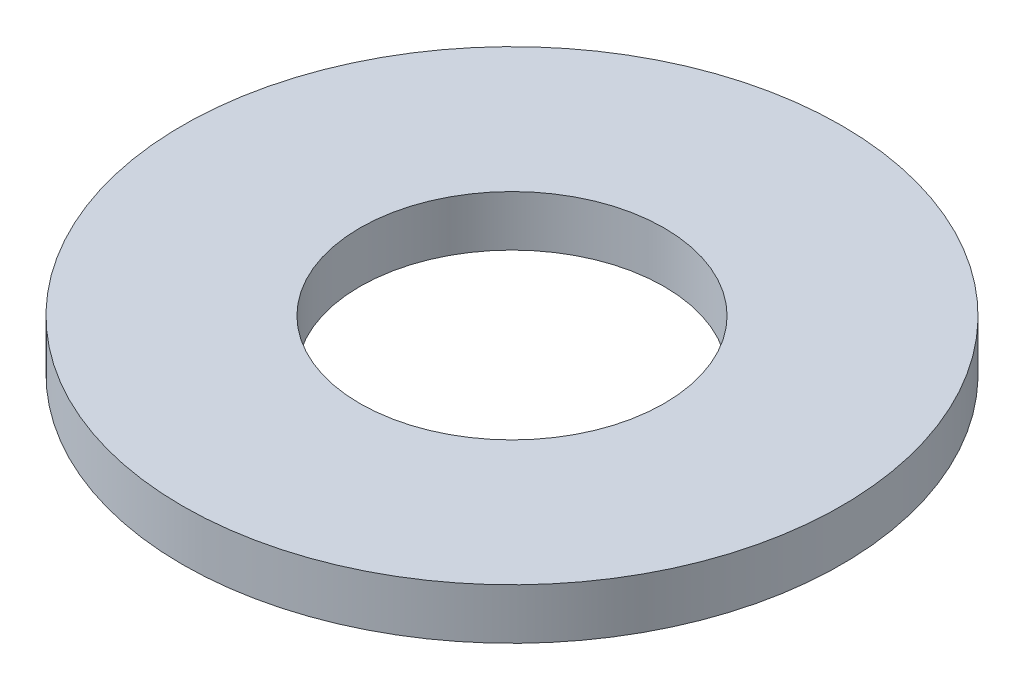
SolidWorks part; units mm, degrees
ref_plane "Front Plane" through (0, 0, 0) normal (0, 0, 1) x (1, 0, 0)
ref_plane "Top Plane" through (0, 0, 0) normal (0, 1, 0) x (1, 0, 0)
ref_plane "Right Plane" through (0, 0, 0) normal (1, 0, 0) x (0, 0, -1)
sketch "Sketch1" plane through (0, 0, 0) normal (0, 1, 0) x (1, 0, 0)
  circle A0 centre (0, 0) radius 97.5
  dimension "FLANGE_OD" = 195
extrude "Boss-Extrude1" add sketch "Sketch1" along normal blind 15
sketch "Sketch2" plane through (0, 0, 0) normal (0, 1, 0) x (1, 0, 0)
  circle A0 centre (0, 0) radius 45
  dimension "BORE_D" = 90
extrude "Cut-Extrude1" cut sketch "Sketch2" along normal through all
sketch "Sketch3" plane through (0, 15, 0) normal (0, 1, 0) x (1, 0, 0)
  circle A0 centre (0, 0) radius 29.4954 construction
  circle A1 centre (-29.4954, 0) radius 2.4154
  dimension "BOLT_D" = 4.8307
  dimension "BOLT_PCD" = 58.9908
extrude "Cut-Extrude2" cut sketch "Sketch3" against normal blind 13.2338 rebuild error yes
pattern_circular "CirPattern1" count 8 over 360 rebuild error yes
